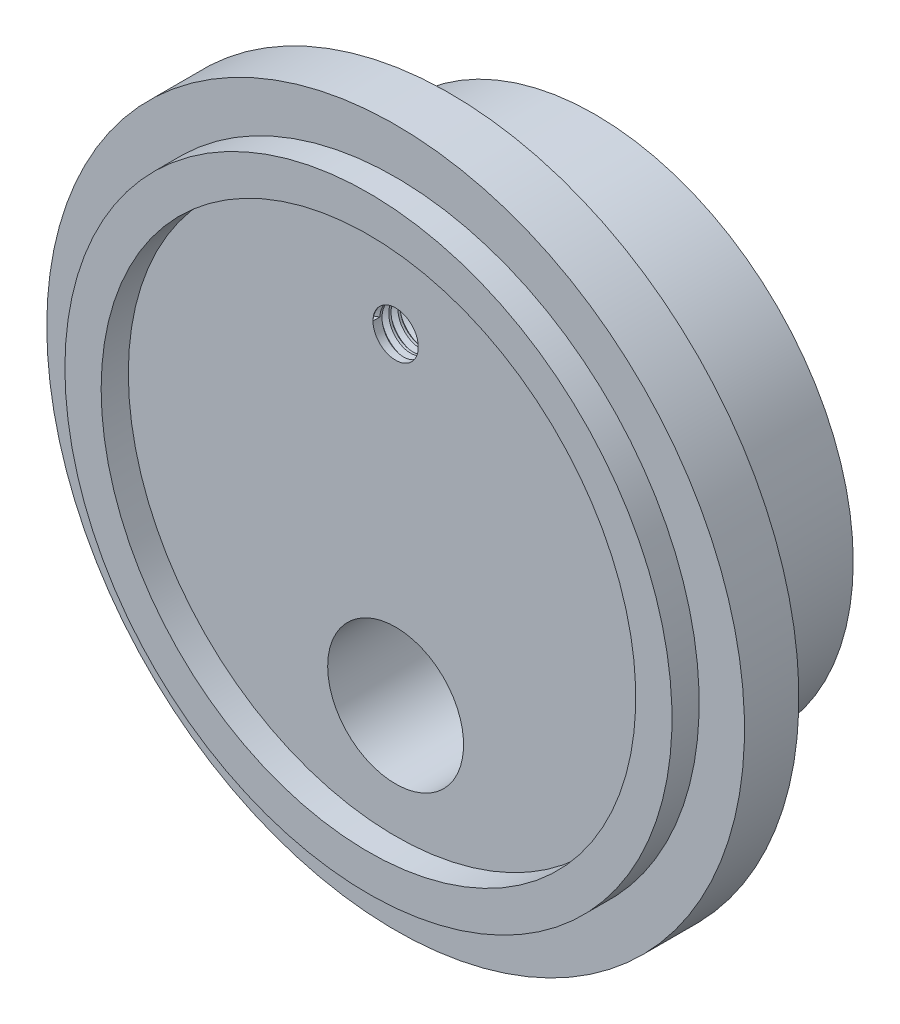
SolidWorks part; units mm, degrees
material "AISI 316 Annealed Stainless Steel Bar (SS)"
ref_plane "Front Plane" through (0, 0, 0) normal (0, 0, 1) x (1, 0, 0)
ref_plane "Top Plane" through (0, 0, 0) normal (0, 1, 0) x (1, 0, 0)
ref_plane "Right Plane" through (0, 0, 0) normal (1, 0, 0) x (0, 0, -1)
sketch "Sketch1" plane through (0, 0, 0) normal (0, 1, 0) x (1, 0, 0)
  line L0 (0, 0) -> (28.5, 0)
  line L1 (28.5, 0) -> (28.5, -16)
  line L2 (28.5, -16) -> (38.5, -16)
  line L3 (38.5, -16) -> (38.5, -22)
  line L4 (38.5, -22) -> (33.5, -22)
  line L5 (33.5, -22) -> (33.5, -25)
  line L6 (33.5, -25) -> (29.5, -25)
  line L8 (28.5, -22) -> (0, -22)
  line L9 (0, -22) -> (0, 0)
  line L10 (0, -22) -> (0, -43.0506) construction
  line L11 (28.5, -22) -> (29.5, -22)
  line L12 (29.5, -22) -> (29.5, -25)
  dimension "D1" = 28.5
  dimension "D2" = 5
  dimension "D4" = 28.5
  dimension "D5" = 22
  dimension "D7" = 3
  dimension "D8" = 6
  dimension "D9" = 4
  dimension "D10" = 1
revolve "Revolve1" add sketch "Sketch1" angle 360 about L10
sketch "Sketch2" plane through (0, 0, 0) normal (0, 0, -1) x (-1, 0, 0)
  circle A1 centre (0, -17) radius 7.5
  point P8 (0, 0)
extrude "Cut-Extrude1" cut sketch "Sketch2" against normal through all
thread "Thread1" pitch 1 method cut profile "Thread Profile1" start angle 0, offset 0, length 7, pitch 1, diameter 15
ref_plane "Plane1" through (7.5, -17, 0) normal (0, -1, 0) x (1, 0, 0)
sketch "Thread Profile1" plane through (7.5, -17, 0) normal (0, -1, 0) x (1, 0, 0)
  line L0 (0, 0) -> (0, 1) construction
  line L1 (0, 0) -> (0.5413, 0.3125)
  line L2 (0.5413, 0.3125) -> (0.5413, 0.4375)
  line L3 (0.5413, 0.4375) -> (0, 0.75)
  line L4 (0.5413, 0.375) -> (0, 0.375) construction
  line L11 (0, 0) -> (0, 0.75)
  point P2 (0, 0)
  dimension "Pitch" = 1
  dimension "Profile_Angle" = 60
  dimension "Profile_Land" = 0.125
  dimension "Profile_Height" = 0.5413
ref_axis "Axis1" through (0, -17, 33.7116) along (0, 0, -1)
sketch "Sketch3" plane through (0, 0, 0) normal (0, 0, -1) x (-1, 0, 0)
  circle A1 centre (0, 18.5) radius 5
  dimension "D1" = 10
extrude "Cut-Extrude2" cut sketch "Sketch3" against normal blind 15
sketch "Sketch4" plane through (0, 0, 0) normal (0, 0, -1) x (-1, 0, 0)
  circle A0 centre (0, 18.5) radius 2.5
  dimension "D1" = 5
extrude "Cut-Extrude3" cut sketch "Sketch4" against normal through all
thread "Thread2" pitch 1 method cut profile "Thread Profile2" start angle 0, offset 0, length 0, pitch 1, diameter 10
ref_plane "Plane2" through (5, 18.5, 0) normal (0, -1, 0) x (1, 0, 0)
sketch "Thread Profile2" plane through (5, 18.5, 0) normal (0, -1, 0) x (1, 0, 0)
  line L0 (0, 0) -> (0, 1) construction
  line L1 (0, 0) -> (0.5413, 0.3125)
  line L2 (0.5413, 0.3125) -> (0.5413, 0.4375)
  line L3 (0.5413, 0.4375) -> (0, 0.75)
  line L4 (0.5413, 0.375) -> (0, 0.375) construction
  line L11 (0, 0) -> (0, 0.75)
  point P2 (0, 0)
  dimension "Pitch" = 1
  dimension "Profile_Angle" = 60
  dimension "Profile_Land" = 0.125
  dimension "Profile_Height" = 0.5413
ref_axis "Axis2" through (0, 18.5, 31.2345) along (0, 0, -1)
thread "Thread3" pitch 1 method cut profile "Thread Profile3" start angle 0, offset 0, length 10, pitch 1, diameter 5
ref_plane "Plane3" through (-2.5, 18.5, 22) normal (0, -1, 0) x (-1, 0, 0)
sketch "Thread Profile3" plane through (-2.5, 18.5, 22) normal (0, -1, 0) x (-1, 0, 0)
  line L0 (0, 0) -> (0, 1) construction
  line L1 (0, 0) -> (0.5413, 0.3125)
  line L2 (0.5413, 0.3125) -> (0.5413, 0.4375)
  line L3 (0.5413, 0.4375) -> (0, 0.75)
  line L4 (0.5413, 0.375) -> (0, 0.375) construction
  line L11 (0, 0) -> (0, 0.75)
  point P2 (0, 0)
  dimension "Pitch" = 1
  dimension "Profile_Angle" = 60
  dimension "Profile_Land" = 0.125
  dimension "Profile_Height" = 0.5413
